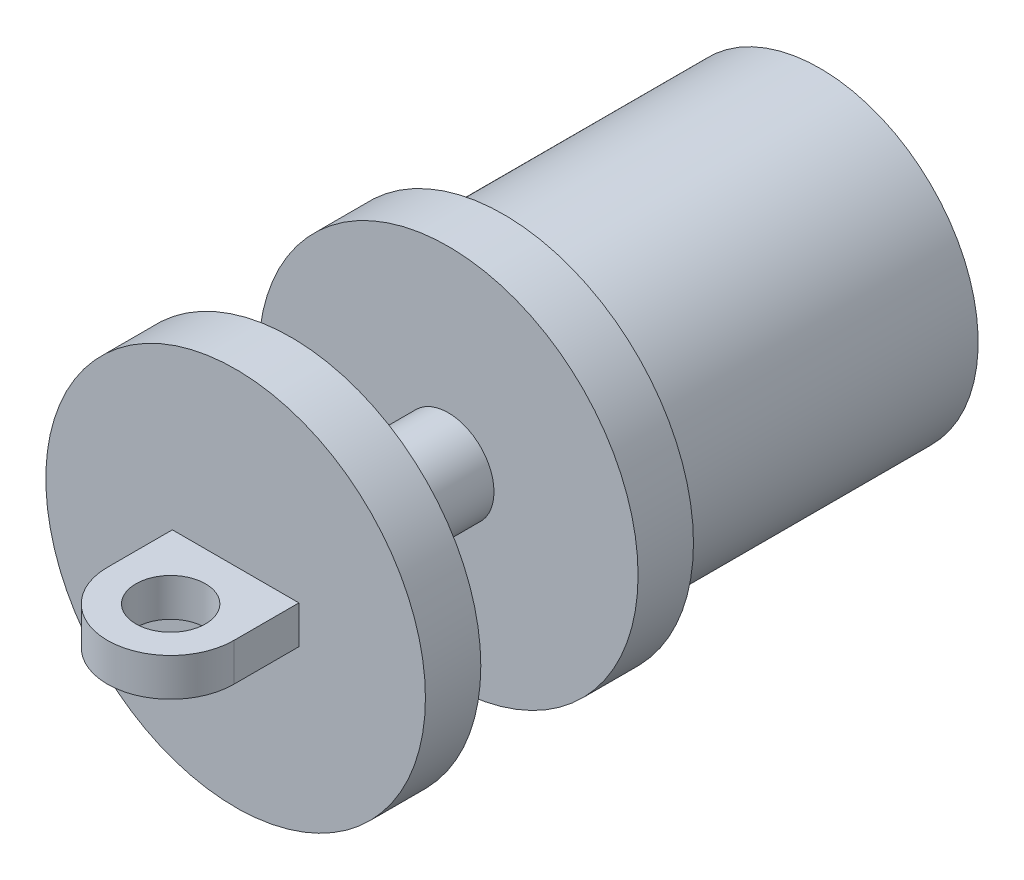
SolidWorks part; units mm, degrees
ref_plane "Front Plane" through (0, 0, 0) normal (0, 0, 1) x (1, 0, 0)
ref_plane "Top Plane" through (0, 0, 0) normal (0, 1, 0) x (1, 0, 0)
ref_plane "Right Plane" through (0, 0, 0) normal (1, 0, 0) x (0, 0, -1)
sketch "Sketch2" plane through (0, 0, 0) normal (0, 0, 1) x (1, 0, 0)
  circle A0 centre (0, 0) radius 15
  dimension "D1" = 30
sketch "Sketch3" plane through (0, 0, 0) normal (1, 0, 0) x (0, 0, -1)
  line L0 (-6.2146, 3.6112) -> (6.2146, 3.6112)
  line L1 (10.591, 15) -> (6.2146, 15)
  line L2 (10.591, 15) -> (10.591, 0)
  line L4 (-10.591, 15) -> (-10.591, 0)
  line L5 (10.591, 15) -> (0, 0) construction
  line L6 (0, 0) -> (-10.591, 15) construction
  line L7 (-6.2146, 15) -> (-6.2146, 3.6112)
  line L8 (0, 15) -> (0, -15) construction
  line L9 (55, 0) -> (-55, 0) construction
  line L10 (-10.591, 0) -> (10.591, 0) construction
  line L13 (0, 55) -> (0, -55) construction
  line L15 (6.2146, 15) -> (6.2146, 3.6112)
  line L16 (-6.2146, 15) -> (-10.591, 15)
  line L18 (-10.591, 0) -> (10.591, 0)
  point P18 (0, -3.6112)
  point P19 (0, 3.6112)
revolve "Revolve2" add sketch "Sketch3" angle 360 about L18
sketch "Sketch4" plane through (0, 0, 0) normal (0, 1, 0) x (1, 0, 0)
  line L0 (-5, -15.7238) -> (-5, -10.591)
  line L1 (-15, -10.591) -> (15, -10.591) construction
  line L2 (-5, -10.591) -> (5, -10.591)
  line L3 (5, -10.591) -> (5, -15.7238)
  circle A0 centre (0, -15.7238) radius 2.75
  arc A1 (-5, -15.7238) -> (5, -15.7238) centre (0, -15.7238) ccw
  dimension "D1" = 5.5
  dimension "D2" = 10
extrude "Boss-Extrude1" add sketch "Sketch4" along normal mid plane 3
sketch "Sketch5" plane through (0, 0, -10.591) normal (0, 0, -1) x (-1, 0, 0)
  circle A0 centre (0, 0) radius 12.5
  dimension "D1" = 25
extrude "Boss-Extrude2" add sketch "Sketch5" along normal blind 25
